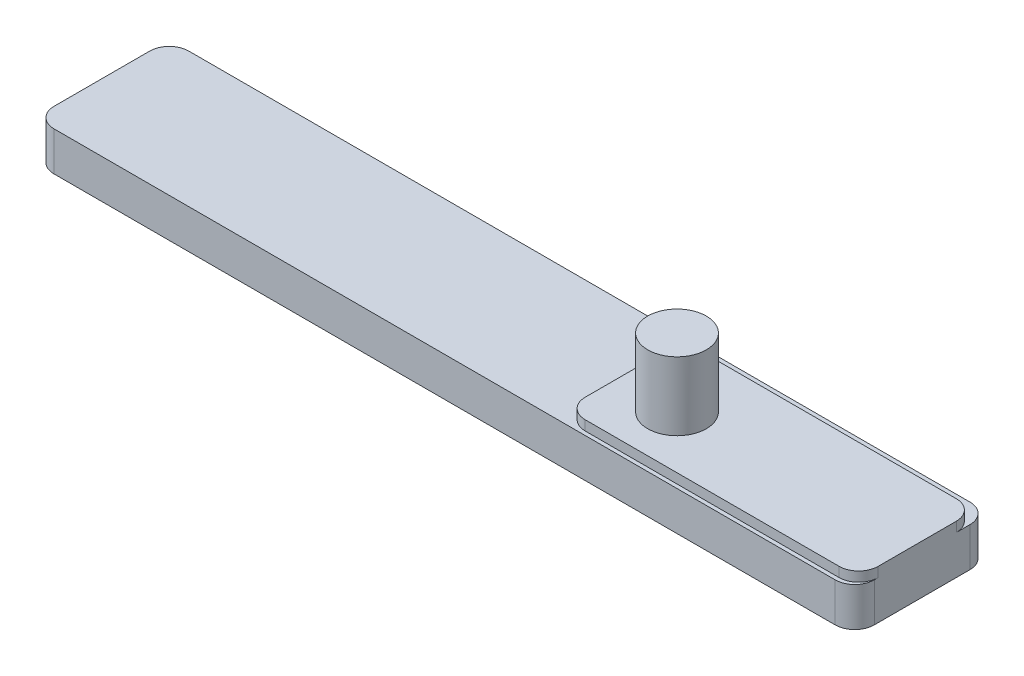
SolidWorks part; units mm, degrees
ref_plane "前视基准面" through (0, 0, 0) normal (0, 0, 1) x (1, 0, 0)
ref_plane "上视基准面" through (0, 0, 0) normal (0, 1, 0) x (1, 0, 0)
ref_plane "右视基准面" through (0, 0, 0) normal (1, 0, 0) x (0, 0, -1)
other "Configuration Table"
sketch "草图1" plane through (0, 0, 0) normal (0, 1, 0) x (1, 0, 0)
  line L1 (0, 0) -> (42, 0)
  line L2 (0, 0) -> (0, 7.4)
  line L3 (0, 7.4) -> (42, 7.4)
  line L4 (42, 0) -> (42, 7.4)
  line L5 (0, 0) -> (42, 7.4) construction
  line L6 (0, 7.4) -> (42, 0) construction
  point P4 (21, 3.7)
  dimension "D1" = 7.4
  dimension "D2" = 42
extrude "凸台-拉伸1" add sketch "草图1" along normal blind 2.5
sketch "草图2" plane through (0, 2.5, 0) normal (0, 1, 0) x (1, 0, 0)
  line L0 (0, 0) -> (42, 0) construction
  line L3 (42, 0) -> (42, 7.4) construction
  circle A0 centre (30, 3.4) radius 1.5
  dimension "D1" = 3
  dimension "D2" = 3.4
  dimension "D3" = 12
extrude "凸台-拉伸2" add sketch "草图2" along normal blind 3.5
sketch "草图3" plane through (0, 2.5, 0) normal (0, 1, 0) x (1, 0, 0)
  line L0 (0, 0) -> (42, 0) construction
  line L1 (0, 7.4) -> (27, 7.4)
  line L2 (0, 7.4) -> (0, 0)
  line L3 (0, 0) -> (27, 0)
  line L4 (27, 7.4) -> (27, 0)
  line L5 (0, 7.4) -> (27, 0) construction
  line L6 (0, 0) -> (27, 7.4) construction
  point P4 (13.5, 3.7)
  dimension "D1" = 27
extrude "切除-拉伸1" cut sketch "草图3" against normal blind 0.5
sketch "草图4" plane through (0, 2.5, 0) normal (0, 1, 0) x (1, 0, 0)
  line L0 (42, 0) -> (42, 7.4) construction
  line L1 (27, 7.4) -> (42, 7.4)
  line L2 (27, 7.4) -> (27, 6.7)
  line L3 (27, 6.7) -> (42, 6.7)
  line L4 (42, 7.4) -> (42, 6.7)
  line L5 (27, 7.4) -> (42, 6.7) construction
  line L6 (27, 6.7) -> (42, 7.4) construction
  line L8 (27, 0) -> (42, 0)
  line L9 (27, 0) -> (27, 0.7)
  line L10 (27, 0.7) -> (42, 0.7)
  line L11 (42, 0) -> (42, 0.7)
  line L12 (27, 0) -> (42, 0.7) construction
  line L13 (27, 0.7) -> (42, 0) construction
  point P4 (34.5, 7.05)
  point P12 (34.5, 0.35)
  dimension "D1" = 0.7
  dimension "D2" = 0.7
extrude "切除-拉伸2" cut sketch "草图4" against normal up to surface (0.5 mm away) up to face at (13.5, 2, -3.7)
sketch "草图5" plane through (0, 2, 0) normal (0, 1, 0) x (1, 0, 0)
  line L0 (42, 0.7) -> (42, 0) construction
  line L1 (0, 0) -> (42, 0)
  line L2 (0, 0) -> (0, 0.5)
  line L3 (0, 0.5) -> (42, 0.5)
  line L4 (42, 0) -> (42, 0.5)
  line L5 (0, 0) -> (42, 0.5) construction
  line L6 (0, 0.5) -> (42, 0) construction
  point P4 (21, 0.25)
  dimension "D1" = 0.5
extrude "切除-拉伸3" cut sketch "草图5" against normal up to next
fillet "圆角1" radius 1 6 edges at (42, 2.25, -0.7) (42, 2.25, -6.7) (0, 1, -7.4) (27, 2.25, -0.7) (27, 2.25, -6.7) (0, 1, -0.5)
fillet "圆角2" radius 1 2 edges at (42, 1, -7.4) (42, 1, -0.5)
